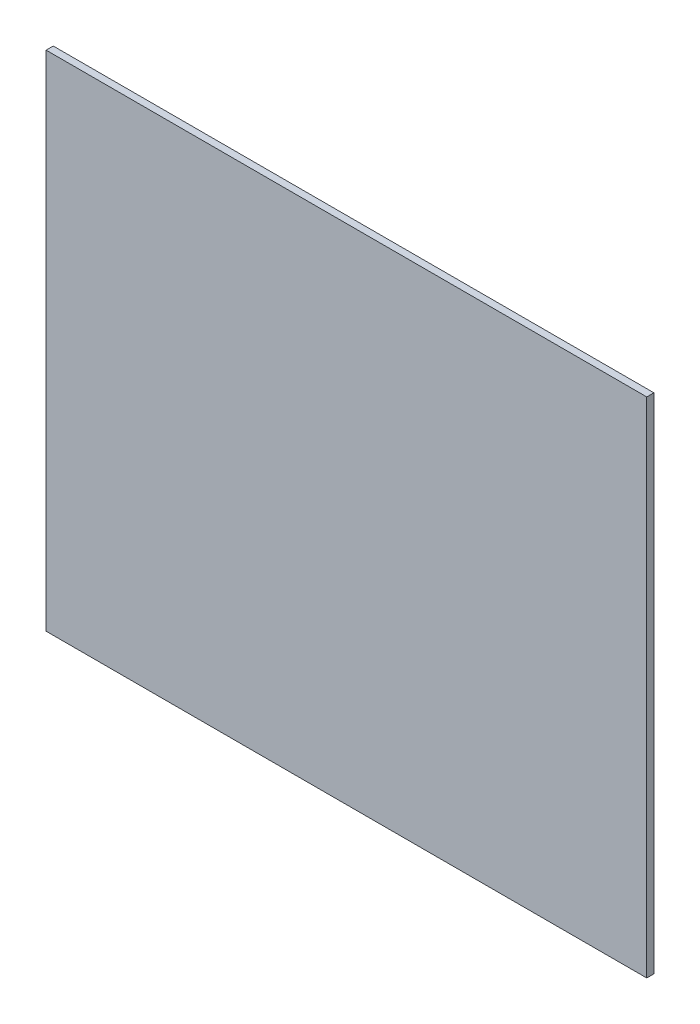
SolidWorks part; units mm, degrees
material "아크릴(내충격성)"
ref_plane "정면" through (0, 0, 0) normal (0, 0, 1) x (1, 0, 0)
ref_plane "윗면" through (0, 0, 0) normal (0, 1, 0) x (1, 0, 0)
ref_plane "우측면" through (0, 0, 0) normal (1, 0, 0) x (0, 0, -1)
sketch "스케치1" plane through (0, 0, 0) normal (0, 0, 1) x (1, 0, 0)
  line L1 (-210, 175.945) -> (210, 175.945)
  line L2 (-210, 175.945) -> (-210, -175.945)
  line L3 (-210, -175.945) -> (210, -175.945)
  line L4 (210, 175.945) -> (210, -175.945)
  line L5 (-210, 175.945) -> (210, -175.945) construction
  line L6 (-210, -175.945) -> (210, 175.945) construction
  point P0 (0, 0)
  dimension "D1" = 351.89
  dimension "D2" = 420
extrude "보스-돌출1" add sketch "스케치1" along normal blind 5
